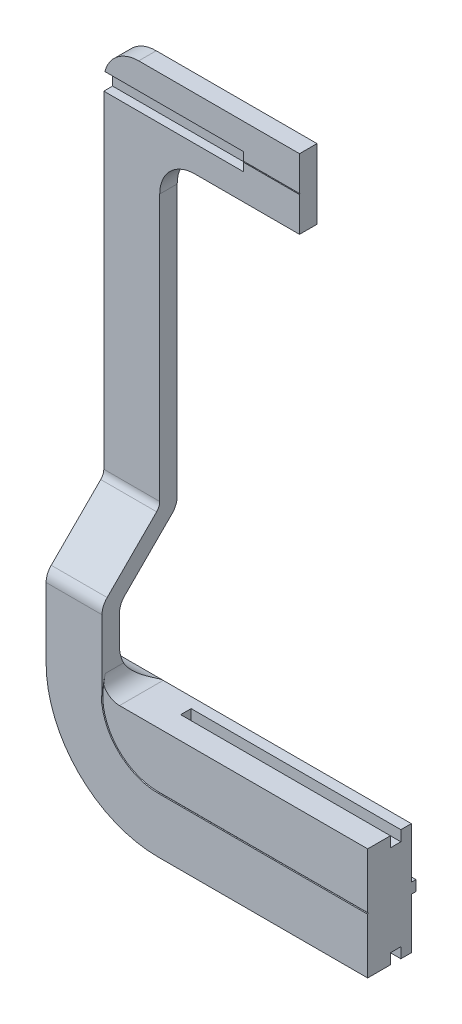
SolidWorks part; units mm, degrees
ref_plane "Front Plane" through (0, 0, 0) normal (1, 0, 0) x (0, 1, 0)
ref_plane "Top Plane" through (0, 0, 0) normal (0, 0, 1) x (0, 1, 0)
ref_plane "Right Plane" through (0, 0, 0) normal (0, 1, 0) x (-1, 0, 0)
sketch "Sketch1" plane through (0, 0, 0) normal (1, 0, 0) x (0, 1, 0)
  line L0 (0, 0) -> (0, 3)
  line L1 (0, 3) -> (3, 3)
  line L2 (3, 3) -> (3, 6)
  line L3 (3, 6) -> (0, 6)
  line L4 (0, 6) -> (0, 12.5)
  line L5 (0, 12.5) -> (15.8, 12.5)
  line L6 (15.8, 12.5) -> (15.9646, 12.3354)
  line L7 (16.0354, 12.3354) -> (16.2, 12.5)
  line L8 (16.2, 12.5) -> (32, 12.5)
  line L9 (32, 12.5) -> (32, 6)
  line L10 (32, 6) -> (29, 6)
  line L11 (29, 6) -> (29, 3)
  line L12 (29, 3) -> (32, 3)
  line L13 (32, 3) -> (32, 0)
  line L14 (32, 0) -> (17.5, 0)
  line L15 (17.5, 0) -> (17.5, -1.3)
  line L16 (17.5, -1.3) -> (14.5, -1.3)
  line L17 (14.5, -1.3) -> (14.5, 0)
  line L18 (14.5, 0) -> (0, 0)
  arc A0 (15.9646, 12.3354) -> (16.0354, 12.3354) centre (16, 12.3707) ccw
  point P20 (14.5, -0.65)
  point P22 (0, 0)
  dimension "D17" = 0.05
  dimension "D1" = 6.5
  dimension "D2" = 3
  dimension "D3" = 3
  dimension "D4" = 15.8
  dimension "D5" = 3
  dimension "D6" = 15.8
  dimension "D7" = 6.5
  dimension "D8" = 3
  dimension "D9" = 3
  dimension "D10" = 3
  dimension "D11" = 3
  dimension "D12" = 3
  dimension "D13" = 3
  dimension "D14" = 1.3
  dimension "D15" = 14.5
  dimension "D16" = 14.5
extrude "Boss-Extrude1" add sketch "Sketch1" against normal blind 60
sketch "Sketch2" plane through (-60, 0, 0) normal (-1, 0, 0) x (0, -1, 0)
  line L0 (-32, 12.5) -> (-32, 0)
  line L1 (-32, 0) -> (0, 0)
  line L2 (0, 0) -> (0, 12.5)
  line L3 (0, 12.5) -> (-15.8, 12.5)
  line L4 (-15.8, 12.5) -> (0, 12.5) construction
  line L7 (-16.2, 12.5) -> (-32, 12.5)
  line L8 (-15.8, 12.5) -> (-16, 12.3)
  line L9 (-16, 12.3) -> (-16.2, 12.5)
revolve "Revolve1" add sketch "Sketch2" angle 90 about L0
sketch "Sketch3" plane through (0, 32, 0) normal (0, 1, 0) x (-1, 0, 0)
  line L0 (92, 12.5) -> (76, 12.5)
  line L1 (92, 12.5) -> (60, 12.5) construction
  line L2 (76, 12.5) -> (76, 7.5)
  line L3 (76, 7.5) -> (92, 7.5)
  line L4 (92, 0) -> (92, 12.5) construction
  line L5 (92, 7.5) -> (92, 12.5)
  dimension "D1" = 5
extrude "Boss-Extrude2" add sketch "Sketch3" along normal blind 20
sketch "Sketch4" plane through (0, 52, 0) normal (0, 1, 0) x (-1, 0, 0)
  line L1 (76, 7.5) -> (92, 7.5)
  line L2 (76, 7.5) -> (76, 12.5)
  line L3 (76, 12.5) -> (92, 12.5)
  line L4 (92, 7.5) -> (92, 12.5)
revolve "Revolve2" add sketch "Sketch4" angle 45 about L1
sketch "Sketch5" plane through (0, 22.25, -22.25) normal (0, 0.7071, -0.7071) x (-1, 0, 0)
  line L1 (76, 42.0729) -> (92, 42.0729)
  line L2 (76, 42.0729) -> (76, 47.0729)
  line L3 (76, 47.0729) -> (92, 47.0729)
  line L4 (92, 42.0729) -> (92, 47.0729)
extrude "Boss-Extrude3" add sketch "Sketch5" along normal blind 21.2726
sketch "Sketch6" plane through (0, 37.292, -37.292) normal (0, 0.7071, -0.7071) x (-1, 0, 0)
  line L1 (76, 47.0729) -> (92, 47.0729)
  line L2 (76, 47.0729) -> (76, 42.0729)
  line L3 (76, 42.0729) -> (92, 42.0729)
  line L4 (92, 47.0729) -> (92, 42.0729)
revolve "Revolve3" add sketch "Sketch6" angle 45 about L1
sketch "Sketch8" plane through (0, 70.5775, 0) normal (0, 1, 0) x (-1, 0, 0)
  line L1 (76, -4.0065) -> (92, -4.0065)
  line L2 (76, -4.0065) -> (76, -9.0065)
  line L3 (76, -9.0065) -> (92, -9.0065)
  line L4 (92, -4.0065) -> (92, -9.0065)
extrude "Boss-Extrude4" add sketch "Sketch8" along normal blind 107.42
sketch "Sketch9" plane through (0, 177.9975, 0) normal (0, 1, 0) x (-1, 0, 0)
  line L1 (76, -9.0065) -> (92, -9.0065)
  line L2 (76, -9.0065) -> (76, -4.0065)
  line L3 (76, -4.0065) -> (92, -4.0065)
  line L4 (92, -9.0065) -> (92, -4.0065)
sketch "Sketch11" plane through (-76, 0, 0) normal (1, 0, 0) x (0, 1, 0)
  line L0 (177.9975, -9.0065) -> (70.5775, -9.0065) construction
  line L1 (177.9975, -4.0065) -> (157.9975, -4.0065)
  line L2 (177.9975, -4.0065) -> (177.9975, -9.0065)
  line L3 (177.9975, -9.0065) -> (157.9975, -9.0065)
  line L4 (157.9975, -4.0065) -> (157.9975, -9.0065)
  dimension "D1" = 20
extrude "Boss-Extrude5" add sketch "Sketch11" along normal blind 40
fillet "Fillet1" radius 10 1 edges at (-76, 157.9975, -6.5065)
fillet "Fillet2" radius 10 1 edges at (-92, 177.9975, -6.5065)
fillet "Fillet3" radius 3 1 edges at (-84, 70.5775, -4.0065)
fillet "Fillet4" radius 5 1 edges at (-84, 52, 7.5)
fillet "Fillet5" radius 10 1 edges at (-84, 32, 7.5)
fillet "Fillet6" radius 5 1 edges at (-76, 32, 6.15)
sketch "Sketch12" plane through (0, 0, -4.0065) normal (0, 0, 1) x (1, 0, 0)
  line L0 (-92, 167.9975) -> (-92, 71.8202) construction
  line L1 (-92, 165.4975) -> (-52, 165.4975)
  line L2 (-92, 165.4975) -> (-92, 170.4975)
  line L3 (-92, 170.4975) -> (-52, 170.4975)
  line L4 (-52, 165.4975) -> (-52, 170.4975)
  line L5 (-82, 177.9975) -> (-36, 177.9975) construction
  dimension "D1" = 5
  dimension "D2" = 40
  dimension "D3" = 7.5
extrude "Cut-Extrude1" cut sketch "Sketch12" against normal blind 2.5
sketch "Sketch13" plane through (-36, 0, 0) normal (1, 0, 0) x (0, 1, 0)
  line L0 (167.9975, -4.0065) -> (167.8561, -4.0065)
  line L1 (177.9975, -4.0065) -> (157.9975, -4.0065) construction
  line L2 (167.8561, -4.0065) -> (167.9975, -4.1479)
  line L3 (167.9975, -4.1479) -> (168.139, -4.0065)
  line L4 (168.139, -4.0065) -> (167.9975, -4.0065)
  line L5 (177.9975, -9.0065) -> (177.9975, -4.0065) construction
  point P4 (0, 0)
  dimension "D1" = 0.2
  dimension "D2" = 0.1414
  dimension "D3" = 10
extrude "Cut-Extrude2" cut sketch "Sketch13" against normal blind 40
fillet "Fillet7" radius 0.02 1 edges at (-44, 167.9975, -4.1479)
